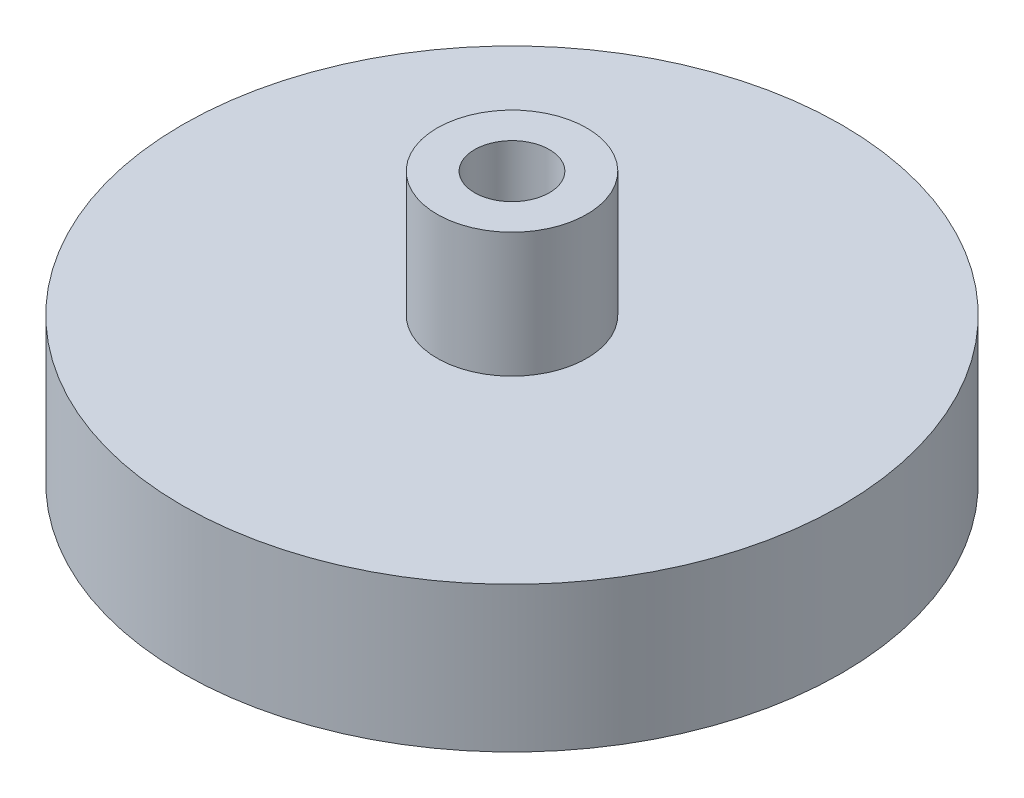
SolidWorks part; units mm, degrees
ref_plane "Front Plane" through (0, 0, 0) normal (0, 0, 1) x (1, 0, 0)
ref_plane "Top Plane" through (0, 0, 0) normal (0, 1, 0) x (1, 0, 0)
ref_plane "Right Plane" through (0, 0, 0) normal (1, 0, 0) x (0, 0, -1)
sketch "Sketch1" plane through (0, 0, 0) normal (0, 0, 1) x (1, 0, 0)
  line L2 (0, 51.7877) -> (0, -60.5028) construction
  line L3 (-13.2202, 14.7478) -> (-13.2202, 22.4)
  line L4 (-13.2202, 22.4) -> (0, 22.4)
  line L5 (-13.2202, 14.7478) -> (0, 14.7478)
  line L6 (0, 14.7478) -> (0, 22.4)
  dimension "D1" = 22.4
revolve "Revolve1" add sketch "Sketch1" angle 360 about L2
sketch "Sketch3" plane through (0, 0, 0) normal (0, 0, 1) x (1, 0, 0)
  line L0 (-33.5065, 16.5756) -> (-33.5065, -28.9466)
  line L1 (-33.5065, -28.9466) -> (32.397, -28.9466)
  line L2 (32.397, -28.9466) -> (32.397, 16.5756)
  line L3 (32.397, 16.5756) -> (-33.5065, 16.5756)
extrude "Cut-Extrude1" cut sketch "Sketch3" against normal mid plane 50
sketch "Sketch4" plane through (0, 0, 0) normal (0, 0, 1) x (1, 0, 0)
  line L0 (0, 0) -> (0, 20.9)
  line L1 (0, 0) -> (0, -20.9)
  line L2 (0, 39.939) -> (0, -32.064) construction
  arc A0 (0, -20.9) -> (0, 20.9) centre (0, 0) cw
  dimension "D1" = 20.9
revolve "Cut-Revolve1" cut sketch "Sketch4" angle 360 about L2
sketch "Sketch5" plane through (0, 0, 0) normal (0, 1, 0) x (1, 0, 0)
  circle A0 centre (0, 0) radius 1.5
  dimension "D1" = 3
extrude "Cut-Extrude2" cut sketch "Sketch5" against normal mid plane 50
sketch "Sketch7" plane through (0, 22.4, 0) normal (0, 1, 0) x (1, 0, 0)
  circle A0 centre (0, 0) radius 3
  circle A1 centre (0, 0) radius 1.5
  dimension "D1" = 1.5
extrude "Boss-Extrude1" add sketch "Sketch7" along normal blind 5
